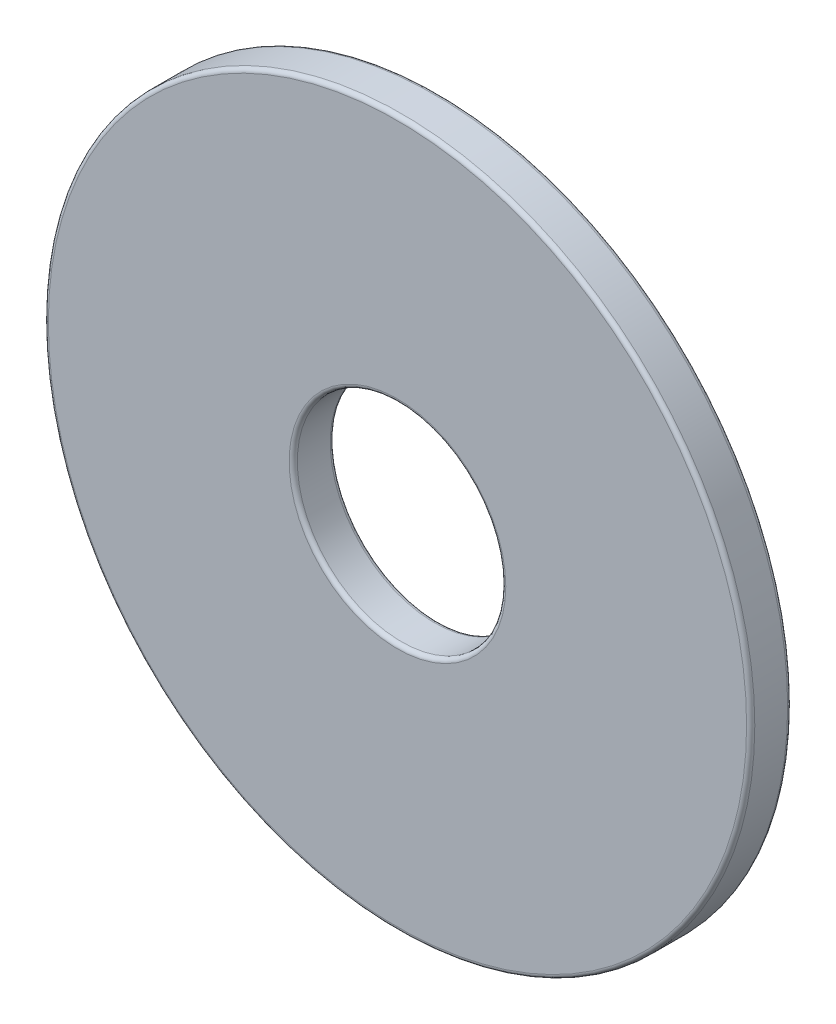
SolidWorks part; units mm, degrees
material "AISI 316 Stainless Steel Sheet (SS)"
ref_plane "Front Plane" through (0, 0, 0) normal (0, 0, 1) x (1, 0, 0)
ref_plane "Top Plane" through (0, 0, 0) normal (0, 1, 0) x (1, 0, 0)
ref_plane "Right Plane" through (0, 0, 0) normal (1, 0, 0) x (0, 0, -1)
sketch "Sketch1" plane through (0, 0, 0) normal (0, 0, 1) x (1, 0, 0)
  circle A0 centre (0, 0) radius 2.5781
  circle A1 centre (0, 0) radius 8.7376
  point P4 (0, 8.7376)
  point P5 (0, 2.5781)
  point P6 (0, -2.5781)
  point P7 (2.5781, 0)
  point P8 (-2.5781, 0)
  dimension "OD" = 17.4752
  dimension "ID" = 5.1562
sketch "Sketch2" plane through (0, 0, 0) normal (1, 0, 0) x (0, 0, -1)
  line L1 (-0.508, 8.7376) -> (0.508, 8.7376)
  line L2 (-0.508, 8.7376) -> (-0.508, -8.7376)
  line L3 (-0.508, -8.7376) -> (0.508, -8.7376)
  line L4 (0.508, 8.7376) -> (0.508, -8.7376)
  point P4 (0, 8.7376)
  point P5 (0.508, 0)
  dimension "Thickness" = 1.016
sketch "Sketch3" plane through (0, 0, 0) normal (0, 0, 1) x (1, 0, 0)
  circle A0 centre (0, 0) radius 2.5781 construction
  circle A1 centre (0, 0) radius 8.7376 construction
  circle A2 centre (0, 0) radius 2.5781
  circle A3 centre (0, 0) radius 8.7376
extrude "Boss-Extrude1" add sketch "Sketch3" against normal up to vertex (0.508 mm away) from vertex up to point (0, 8.7376, -0.508) starting at point (0, 8.7376, 0.508)
fillet "Fillet1" radius 0.1016 4 edges at (2.5781, 0, 0.508) (2.5781, 0, -0.508) (8.7376, 0, 0.508) (8.7376, 0, -0.508)
equation "\"D1@Fillet1\"=\"Thickness@Sketch2\"*.1"
